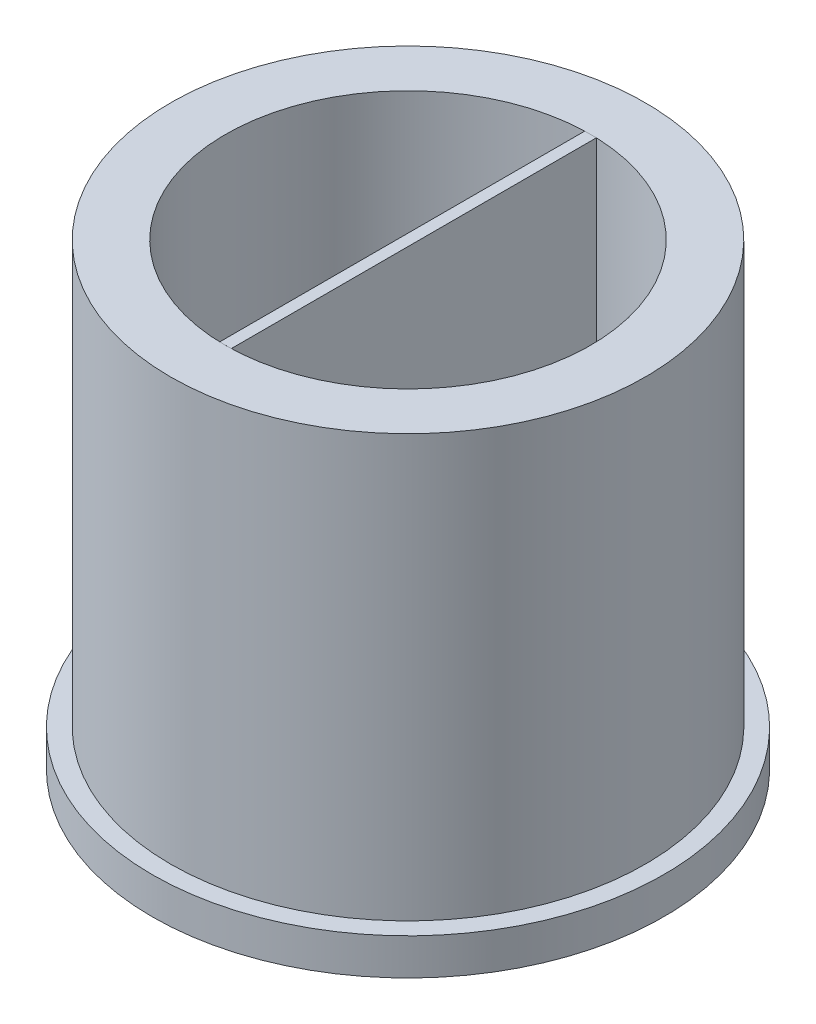
SolidWorks part; units mm, degrees
ref_plane "Front Plane" through (0, 0, 0) normal (0, 0, 1) x (1, 0, 0)
ref_plane "Top Plane" through (0, 0, 0) normal (0, 1, 0) x (1, 0, 0)
ref_plane "Right Plane" through (0, 0, 0) normal (1, 0, 0) x (0, 0, -1)
sketch "Sketch1" plane through (0, 0, 0) normal (0, 1, 0) x (1, 0, 0)
  circle A0 centre (0, 0) radius 130
extrude "Boss-Extrude1" add sketch "Sketch1" along normal blind 241.01
sketch "Sketch2" plane through (0, 241.01, 0) normal (0, 1, 0) x (1, 0, 0)
  circle A0 centre (0, 0) radius 100
extrude "Cut-Extrude1" cut sketch "Sketch2" against normal through all
sketch "Sketch3" plane through (0, 241.01, 0) normal (0, 1, 0) x (1, 0, 0)
  line L0 (0, 0) -> (0, 130) construction
  line L1 (0, 0) -> (0, -128.9732) construction
  line L2 (0, 0) -> (3.175, 0) construction
  line L3 (0, 0) -> (-3.175, 0) construction
  line L4 (3.175, 0) -> (3.175, 99.9496) construction
  line L5 (3.175, 0) -> (3.175, -99.9496) construction
  line L6 (-3.175, 0) -> (-3.175, 99.9496) construction
  line L7 (-3.175, 0) -> (-3.175, -99.9496) construction
  circle A0 centre (0, 0) radius 130 construction
  circle A1 centre (0, 0) radius 100 construction
  arc A2 (-3.175, 99.9496) -> (0, 100) centre (0, 0) ccw
  arc A3 (-3.175, -99.9496) -> (0, -100) centre (0, 0) cw
  arc A4 (0, -100) -> (1.3909, -99.9903) centre (0, 0) cw
sketch "Sketch5" plane through (0, 0, 0) normal (0, 1, 0) x (1, 0, 0)
  line L0 (-3.175, 99.9496) -> (-3.175, -99.9496)
  line L1 (3.175, -99.9496) -> (3.175, 99.9496)
  line L2 (-3.175, 99.9496) -> (3.175, 99.9496)
  line L3 (-3.175, -99.9496) -> (3.175, -99.9496)
extrude "Boss-Extrude2" add sketch "Sketch5" along normal blind 241.01 separate body
sketch "Sketch6" plane through (0, 0, 0) normal (0, 1, 0) x (1, 0, 0)
  circle A0 centre (0, 0) radius 140
  dimension "D1" = 280
extrude "Boss-Extrude8" add sketch "Sketch6" against normal blind 10 separate body contours A0
sketch "Sketch8" plane through (0, 0, 0) normal (0, 1, 0) x (1, 0, 0)
  circle A0 centre (0, 0) radius 130
  circle A1 centre (0, 0) radius 140
extrude "Boss-Extrude10" add sketch "Sketch8" along normal blind 10 separate body
combine bodies "Combine1" operation type add bodies to combine 104 105
